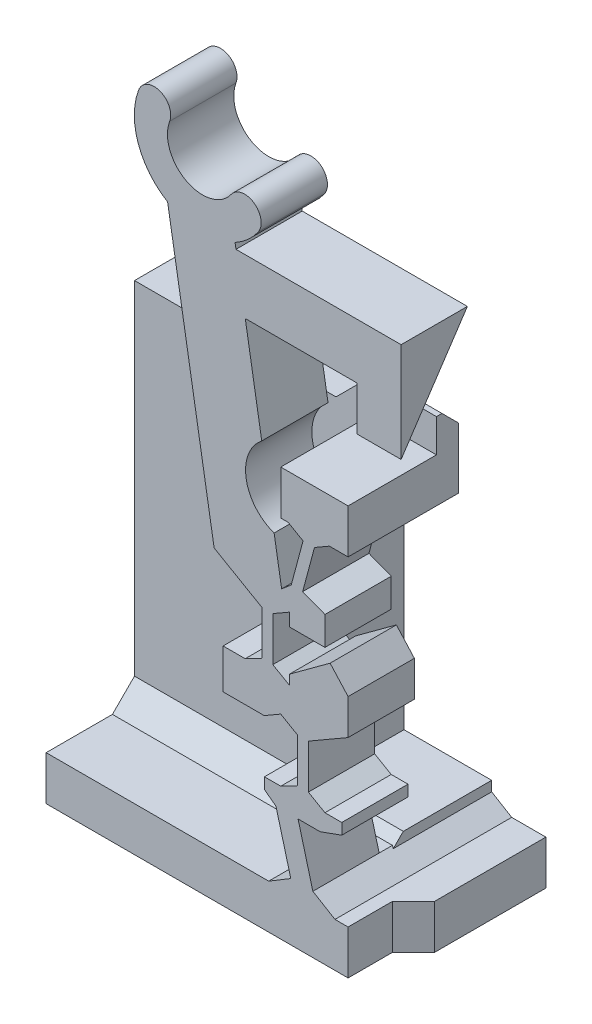
SolidWorks part; units mm, degrees
material "Nylon 6/12"
ref_plane "Front Plane" through (0, 0, 0) normal (0, 0, 1) x (1, 0, 0)
ref_plane "Top Plane" through (0, 0, 0) normal (0, 1, 0) x (1, 0, 0)
ref_plane "Right Plane" through (0, 0, 0) normal (1, 0, 0) x (0, 0, -1)
sketch "Sketch-SkeletonConfigUp" plane through (0, 0, 0) normal (0, 0, 1) x (1, 0, 0)
  line L0 (0, 0) -> (0, -50000) construction
  line L1 (0, 0) -> (4.5811, 6.2164) construction
  line L2 (9.8143, 13.3177) -> (4.5811, 13.945) construction
  line L3 (4.5811, 13.945) -> (2.9713, 10.4094) construction
  line L4 (2.9713, 10.4094) -> (4.5811, 6.2164) construction
  line L5 (4.5811, 13.945) -> (6.2429, 19.1409) construction
  line L6 (2.9713, 10.4094) -> (0.0405, 27.8193) construction
  line L7 (4.5811, 6.2164) -> (9.8143, 13.3177) construction
  line L8 (-587.3593, -797.0242) -> (9.8143, 13.3177) construction
  dimension "D2" = 7.7221
  dimension "D3" = 8.8212
  dimension "D4" = 5.2707
  dimension "D5" = 119.553
  dimension "D6" = 3.8848
  dimension "D7" = 5.4552
  dimension "D8" = 17.6549
  dimension "D9" = 4.4914
  dimension "D10" = 6.745
  dimension "D11" = 145.964
  dimension "D12" = 143.612
sketch "Sketch-SkeletonConfigDown" plane through (0, 0, 0) normal (0, 0, 1) x (1, 0, 0)
  line L0 (0, 0) -> (0, -50000) construction
  line L1 (0, 0) -> (4.5811, 6.2164) construction
  line L2 (9.8143, 13.3177) -> (4.5811, 13.945) construction
  line L3 (4.5811, 13.945) -> (6.1909, 10.4094) construction
  line L4 (6.1909, 10.4094) -> (4.5811, 6.2164) construction
  line L5 (4.5811, 13.945) -> (1.753, 18.6098) construction
  line L6 (6.1909, 10.4094) -> (-8.8652, 19.6294) construction
  line L7 (4.5811, 6.2164) -> (9.8143, 13.3177) construction
  line L8 (-589.9357, -800.5203) -> (9.8143, 13.3177) construction
  dimension "D2" = 7.7221
  dimension "D3" = 8.8212
  dimension "D4" = 5.2707
  dimension "D5" = 119.553
  dimension "D6" = 3.8848
  dimension "D7" = 5.4552
  dimension "D8" = 17.6549
  dimension "D9" = 4.4914
  dimension "D10" = 6.745
  dimension "D11" = 145.964
  dimension "D1" = 143.612
ref_plane "Plane-Cam Base" through (9.128, 0, 0) normal (1, 0, 0) x (0, 0, -1)
ref_plane "Plane-Down-to-Up Derailleur Clearance" through (6.628, 0, 0) normal (1, 0, 0) x (0, 0, -1)
ref_plane "Plane-Cam Cavity Roof" through (5.128, 0, 0) normal (1, 0, 0) x (0, 0, -1)
sketch "Sketch-SwitchBossUp" plane through (0, 0, 0) normal (0, 0, 1) x (1, 0, 0)
  line L0 (3.5811, 11.4759) -> (3.5811, 12.945) construction
  line L5 (5.5811, 12.5552) -> (5.5811, 11.263)
  line L7 (1.5115, 25.1048) -> (1.5536, 24.8548)
  line L8 (-0.4607, 24.7728) -> (1.6885, 12.0057) construction
  line L9 (2.9713, 10.4094) -> (0.0405, 27.8193) construction
  line L11 (0.1364, 21.2256) -> (2.1086, 21.5576) construction
  line L15 (6.628, -23.7286) -> (6.628, 23.7286) construction
  line L16 (2.9713, 10.4094) -> (4.5811, 6.2164) construction
  line L17 (3.5811, 12.945) -> (3.5811, 14.945) construction
  line L18 (5.5811, 12.945) -> (5.5811, 14.945) construction
  line L19 (4.3311, 13.945) -> (4.8311, 13.945) construction
  line L20 (3.5811, 14.945) -> (5.5811, 14.945) construction
  line L21 (3.5811, 12.945) -> (5.5811, 12.945) construction
  line L22 (4.5811, 12.945) -> (4.5811, 14.945) construction
  line L23 (4.5811, 6.2164) -> (8.5405, 7.1023) construction
  line L24 (1.9713, 9.4094) -> (1.9713, 11.4094) construction
  line L25 (3.9713, 9.4094) -> (3.9713, 11.4094) construction
  line L26 (3.9713, 9.4094) -> (1.9713, 9.4094) construction
  line L27 (1.9713, 11.4094) -> (3.9713, 11.4094) construction
  line L28 (3.5811, 7.2164) -> (5.5811, 7.2164) construction
  line L29 (3.5811, 7.2164) -> (3.5811, 5.2164) construction
  line L30 (5.5811, 7.2164) -> (5.5811, 5.2164) construction
  line L31 (3.5811, 5.2164) -> (5.5811, 5.2164) construction
  line L32 (4.8311, 6.2164) -> (4.3311, 6.2164) construction
  line L40 (3.2213, 10.4094) -> (2.7213, 10.4094) construction
  line L66 (0.0405, 27.8193) -> (0.0405, 50027.8193) construction
  line L75 (1.6885, 12.0057) -> (0.5652, 12.6542)
  line L76 (5.5811, 11.263) -> (5.5811, 12.5552) construction
  line L77 (5.5811, 7.6494) -> (6.628, 8.2538)
  line L80 (5.8152, 10.763) -> (6.628, 9.8603)
  line L81 (9.128, 1033.2419) -> (9.128, 20.0586) construction
  line L85 (6.9307, 9.5241) -> (8.5405, 7.7363) construction
  line L88 (5.7256, 17.3347) -> (6.628, 17.3347)
  line L92 (3.7762, 8.3129) -> (6.9307, 9.5241) construction
  line L98 (1.9713, 9.0164) -> (0.9713, 9.0164)
  line L99 (0.9713, 9.0164) -> (0.9713, 7.2164)
  line L100 (0.9713, 7.2164) -> (2.8311, 7.2164)
  line L101 (4.5811, 6.2164) -> (6.9307, 9.5241) construction
  line L103 (0.0405, 27.8193) -> (1.9448, 26.4638) construction
  line L104 (6.9307, 9.5241) -> (8.5405, 7.7363) construction
  line L107 (1.9713, 9.4094) -> (1.9713, 9.0164) construction
  line L109 (0.0405, 27.8193) -> (-2.1498, 28.6358) construction
  line L111 (6.628, 9.8603) -> (6.628, 8.2538)
  line L112 (6.628, 9.8603) -> (6.9307, 9.5241) construction
  line L113 (2.8424, 4.8235) -> (2.8424, 4.3235)
  line L114 (7.3693, 7.7363) -> (7.3563, 7.7363) construction
  line L121 (5.0345, -1.1719) -> (5.0345, 1.4305) construction
  line L122 (9.028, 22.3548) -> (9.028, 20.3548)
  line L127 (5.5811, 15.3347) -> (5.5811, 14.945) construction
  line L130 (6.0345, 0.8281) -> (6.628, 0.8281)
  line L132 (2.8424, 4.3235) -> (3.3646, 3.9305)
  line L133 (2.9713, 10.4094) -> (6.1909, 10.4094) construction
  line L134 (4.5811, 10.4094) -> (4.5811, 13.945) construction
  line L135 (4.5811, 10.4094) -> (4.5811, 6.2164) construction
  line L137 (3.9713, 9.4094) -> (5.5811, 7.2164) construction
  line L139 (5.8152, 10.763) -> (3.9713, 9.4094)
  line L141 (4.0345, 1.4305) -> (3.0345, 0.8281)
  line L142 (3.0345, 0.8281) -> (3.0345, -1.1719)
  line L143 (9.128, 20.0586) -> (9.128, 18.3333) construction
  line L145 (9.128, 16.6071) -> (9.128, -49992.4167) construction
  line L147 (5.5811, 11.263) -> (5.5811, 12.5552) construction
  line L150 (3.0345, -1.1719) -> (5.0345, -1.1719)
  line L151 (3.3646, 3.9305) -> (4.3646, 3.9305) construction
  line L152 (4.5902, 14.945) -> (4.0543, 12.945)
  line L153 (5.1078, 14.945) -> (4.572, 12.945)
  line L157 (3.5811, 17.3347) -> (3.5811, 15.3347)
  line L158 (5.7829, 15.3347) -> (6.628, 15.3347)
  line L162 (3.2213, 11.4094) -> (3.2213, 9.4094)
  line L164 (2.7213, 11.4094) -> (2.7213, 9.4094)
  line L169 (4.3311, 7.2164) -> (4.3311, 5.2164)
  line L170 (4.8311, 5.2164) -> (4.8311, 7.2164)
  line L175 (4.3311, 7.2164) -> (3.5811, 7.6494)
  line L176 (4.8311, 7.2164) -> (5.5811, 7.6494)
  line L177 (5.5811, 7.2164) -> (5.5811, 7.6494) construction
  line L179 (4.3311, 5.2164) -> (3.5811, 4.8235)
  line L180 (3.5811, 5.2164) -> (3.5811, 4.8235) construction
  line L181 (3.5811, 4.8235) -> (2.8424, 4.8235)
  line L183 (4.8311, 5.2164) -> (5.5811, 4.7834)
  line L184 (5.5811, 5.2164) -> (5.5811, 4.7834) construction
  line L186 (9.128, -23.7286) -> (9.128, 23.7286) construction
  line L187 (2.7213, 9.4094) -> (1.9713, 9.0164)
  line L188 (3.2213, 9.4094) -> (3.9713, 8.9764)
  line L189 (3.2213, 11.4094) -> (3.9713, 11.8424)
  line L190 (2.7213, 11.4094) -> (1.6885, 12.0057)
  line L191 (3.9713, 11.4094) -> (3.9713, 11.8424) construction
  line L192 (3.9713, 11.8424) -> (3.9713, 11.263)
  line L193 (4.572, 12.945) -> (5.5811, 12.5552)
  line L194 (4.0543, 12.945) -> (3.6203, 12.5779)
  line L195 (3.9713, 11.263) -> (5.5811, 11.263)
  line L196 (3.9713, 9.4094) -> (3.9713, 8.9764)
  line L197 (3.5811, 7.2164) -> (3.5811, 7.6494) construction
  line L199 (3.5811, 7.6494) -> (2.8311, 7.2164)
  line L201 (2.8424, 4.3235) -> (2.8424, 3.9305) construction
  line L202 (2.8424, 3.9305) -> (3.3646, 3.9305) construction
  line L204 (5.0345, 1.4305) -> (3.0345, 1.4305) construction
  line L205 (3.0345, 1.4305) -> (3.0345, 0.8281) construction
  line L206 (5.0345, 1.4305) -> (6.0345, 0.8281)
  line L207 (9.128, 18.3333) -> (9.128, 16.6071) construction
  line L208 (6.628, -1.1719) -> (6.628, 0.8281)
  line L209 (9.128, 20.0586) -> (9.128, 16.6071) construction
  line L211 (5.0345, 1.4305) -> (4.3646, 3.9305)
  line L212 (4.0345, 1.4305) -> (3.3646, 3.9305)
  line L214 (4.5902, 14.945) -> (3.9152, 15.3347)
  line L215 (3.9152, 15.3347) -> (3.5811, 15.3347)
  line L216 (5.1078, 14.945) -> (5.7829, 15.3347)
  line L217 (5.5811, 12.945) -> (5.5811, 12.5552) construction
  line L218 (5.1078, 14.945) -> (5.1078, 15.3347) construction
  line L219 (5.7829, 15.3347) -> (3.9152, 15.3347) construction
  line L221 (9.028, 22.3548) -> (9.028, 24.8548)
  line L224 (3.5811, 17.3347) -> (5.7256, 17.3347)
  line L232 (6.628, 15.3347) -> (6.628, 17.3347)
  line L233 (6.628, -1.1719) -> (5.0345, -1.1719)
  line L236 (1.5536, 24.8548) -> (9.028, 24.8548)
  line L240 (4.3646, 3.9305) -> (5.3646, 3.9305)
  line L241 (5.3646, 3.9305) -> (6.3424, 4.2834)
  line L248 (7.028, 22.3548) -> (1.9744, 22.3548)
  line L249 (1.9744, 22.3548) -> (2.7198, 17.9273)
  line L250 (9.028, 20.3548) -> (7.028, 20.3548)
  line L251 (7.028, 20.3548) -> (7.028, 22.3548)
  line L252 (3.2801, 14.5986) -> (3.6203, 12.5779)
  line L253 (4.3396, 14.0097) -> (4.8226, 13.8803) construction
  line L254 (0.5652, 12.6542) -> (-1.5413, 25.1678)
  line L367 (5.5811, 4.7834) -> (6.3424, 4.7834)
  line L368 (6.3424, 4.7834) -> (6.3424, 4.2834)
  arc A0 (1.5115, 25.1048) -> (2.5558, 26.0289) centre (0.0405, 27.8193) ccw
  arc A1 (-1.5413, 25.1678) -> (-2.8525, 28.8978) centre (0.0405, 27.8193) cw
  arc A2 (-2.8525, 28.8978) -> (-1.447, 28.3738) centre (-2.1498, 28.6358) cw
  arc A3 (2.5558, 26.0289) -> (1.3338, 26.8987) centre (1.9448, 26.4638) ccw
  arc A4 (-1.447, 28.3738) -> (1.3338, 26.8987) centre (0.0405, 27.8193) ccw
  arc A5 (3.5811, 12.945) -> (3.5811, 14.945) centre (3.2894, 13.945) ccw construction
  arc A6 (5.5811, 12.945) -> (5.5811, 14.945) centre (5.8727, 13.945) cw construction
  arc A7 (2.5699, 9.8686) -> (1.9713, 11.4094) centre (1.6796, 10.4094) ccw construction
  arc A8 (3.9713, 11.4094) -> (3.9713, 9.4094) centre (4.2629, 10.4094) ccw construction
  arc A9 (3.5811, 7.2164) -> (3.5811, 5.2164) centre (3.2895, 6.2164) cw construction
  arc A10 (5.5811, 7.2164) -> (5.5811, 5.2164) centre (5.8728, 6.2164) ccw construction
  circle A28 centre (0.0405, 27.8193) radius 2.3375 construction
  arc A29 (1.9713, 9.4094) -> (2.5699, 9.8686) centre (1.6796, 10.4094) ccw construction
  arc A30 (3.2801, 14.5986) -> (2.7198, 17.9273) centre (3.9114, 16.4164) cw
  arc A31 (-0.4607, 24.7728) -> (-1.5413, 25.1678) centre (0.0405, 27.8193) cw construction
  point P53 (4.5811, 13.945)
  point P63 (2.9713, 10.4094)
  point P93 (1.1225, 21.3916)
  dimension "D23" = 1.5875
  dimension "D24" = 0.75
  dimension "D2" = 2
  dimension "D5" = 2
  dimension "D8" = 42
  dimension "D16" = 42
  dimension "D27" = 120
  dimension "D28" = 120
  dimension "D30" = 120
  dimension "D32" = 120
  dimension "D33" = 120
  dimension "D34" = 120
  dimension "D17" = 0.5
  dimension "D21" = 2
  dimension "D22" = 1
  dimension "D38" = 2
  dimension "D39" = 0.5
  dimension "D40" = 60
  dimension "D41" = 1
  dimension "D42" = 45
  dimension "D43" = 120
  dimension "D10" = 15
  dimension "D12" = 2.5
  dimension "D13" = 1
  dimension "D19" = 1
  dimension "D25" = 15
  dimension "D26" = 120
  dimension "D35" = 120
  dimension "D20" = 3
  dimension "D48" = 2
  dimension "D82" = 1
  dimension "D83" = 3.5
  dimension "D14" = 2.5
  dimension "D15" = 0.25
  dimension "D7" = 2
  dimension "D9" = 2
  dimension "D6" = 0.5
  dimension "D18" = 1.8
  dimension "D29" = 0.5
  dimension "D31" = 1
extrude "Boss-Switch Body" add sketch "Sketch-SwitchBossUp" along normal blind 3
sketch "Sketch1" plane through (0, 0, 0) normal (0, 0, -1) x (-1, 0, 0)
  line L1 (-7.5811, -1.1719) -> (0.4122, -1.1719)
  line L2 (-7.5811, -1.1719) -> (-7.5811, 0.8281)
  line L4 (0.4122, -1.1719) -> (0.4122, 0.8281)
  line L5 (-3.5811, 18.8347) -> (-7.5811, 18.8347)
  line L10 (-7.5811, 18.8347) -> (-7.5811, 15.3347)
  line L11 (-4.0345, 1.4305) -> (-5.0345, 1.4305)
  line L12 (-7.5811, 15.3347) -> (-3.5811, 15.3347)
  line L13 (-4.0345, 1.4305) -> (-3.0345, 0.8281)
  line L14 (-3.5811, 15.3347) -> (-3.5811, 18.8347)
  line L20 (-4.3646, 3.9305) -> (-5.0345, 1.4305) construction
  line L22 (-3.0345, -1.1719) -> (-6.628, -1.1719) construction
  line L23 (-3.0345, 0.8281) -> (0.4122, 0.8281)
  line L24 (-5.0345, 1.4305) -> (-6.0345, 0.8281)
  line L25 (-6.0345, 0.8281) -> (-7.5811, 0.8281)
  dimension "D1" = 3.5
extrude "Boss-Flange Width" add sketch "Sketch1" along normal blind 5
ref_plane "Plane-Sta2Sit Groove" through (0.0405, 0, 0) normal (1, 0, 0) x (0, 0, -1)
ref_plane "Plane-Cam Outer Surface" through (-12.0395, 0, 0) normal (1, 0, 0) x (0, 0, -1)
ref_plane "Plane-FlangeTop" through (-7.0395, 0, 0) normal (1, 0, 0) x (0, 0, -1)
sketch "Sketch2" plane through (-7.0395, 0, 0) normal (1, 0, 0) x (0, 0, -1)
  line L0 (5, 15.3347) -> (-3, 15.3347) construction
  line L1 (5, 17.3347) -> (1, 17.3347)
  line L2 (5, 17.3347) -> (5, 15.3347)
  line L3 (5, 15.3347) -> (1, 15.3347)
  line L4 (1, 17.3347) -> (1, 15.3347)
  line L5 (-3, -1.1719) -> (-3, 0.8281) construction
  line L11 (5, 0.8281) -> (-3, 0.8281)
  line L12 (5, 0.8281) -> (5, -1.1719)
  line L13 (5, -1.1719) -> (-3, -1.1719)
  line L14 (-3, 0.8281) -> (-3, -1.1719)
  line L15 (0, 10.4094) -> (0, 27.8193) construction
  line L17 (5, 0.8281) -> (5, -1.1719) construction
  line L18 (-3, 0.8281) -> (0, 0.8281) construction
  dimension "D1" = 1
  dimension "D2" = 2
extrude "Boss-Flange Height" add sketch "Sketch2" along normal up to surface (11.6675 mm away)
sketch "Sketch10" plane through (0, 15.3347, 0) normal (0, 1, 0) x (1, 0, 0)
  line L0 (9.128, -23.7286) -> (9.128, 23.7286) construction
  line L1 (7.5811, 5) -> (5.128, 5)
  line L2 (7.5811, 5) -> (7.5811, 2)
  line L3 (7.5811, 2) -> (5.128, 2)
  line L5 (4.628, 7) -> (4.628, 1) construction
  line L6 (3.5811, 1) -> (-7.0395, 1) construction
  line L8 (5.128, 5) -> (5.128, 2)
  dimension "D1" = 1
  dimension "D2" = 0.5
  dimension "D3" = 4.5
extrude "Cut-Up-To-Down Derailleur Clearance" cut sketch "Sketch10" along normal up to next
sketch "Sketch17" plane through (0, 15.3347, 0) normal (0, -1, 0) x (1, 0, 0)
  line L0 (5.128, -5) -> (-7.0395, -5)
  line L1 (5.128, -5) -> (-7.0395, -5) construction
  line L2 (-7.0395, -5) -> (-7.0395, -1)
  line L3 (-7.0395, -1) -> (5.128, -1)
  line L4 (5.128, -1) -> (5.128, -5)
  line L5 (-7.0395, -1) -> (-7.0395, -5) construction
extrude "Boss-Flange Support" add sketch "Sketch17" along normal up to surface (14.5065 mm away) up to face at (-2.0025, 0.8281, -1)
sketch "Sketch-HolePositions" plane through (0, -1.1719, 0) normal (0, -1, 0) x (1, 0, 0)
  line L0 (-7.0395, -3) -> (7.5811, -3) construction
  line L1 (7.5811, -5) -> (-7.0395, -5) construction
  line L2 (7.5811, -5) -> (7.5811, 0) construction
  line L4 (-7.0395, -22.2167) -> (-7.0395, 22.2167) construction
  point P6 (-5.0395, -3)
  point P7 (-0.5395, -3)
  dimension "D1" = 2
  dimension "D2" = 4.5
  dimension "D3" = 2
sketch "Sketch6" plane through (0, -1.1719, 0) normal (0, -1, 0) x (-1, 0, 0)
  point P0 (5.0395, 3)
  point P3 (0.5395, 3)
hole_wizard "Tap Drill for M2x0.4 Tap1" positions "Sketch6" profile "Sketch5" hole size "M2x0.4" standard "ANSI Metric" end condition through all
sketch "Sketch5" plane through (-5.0395, -1.1719, -3) normal (1, 0, 0) x (0, 0, -1)
  line L0 (0, 0) -> (0, 30.5577)
  line L1 (0, 30.5577) -> (0.8, 30.5577)
  line L2 (0.8, 30.5577) -> (0.8, 0)
  line L5 (0.8, 0) -> (0, 0)
  line L11 (0, -6.35) -> (0, 107.95) construction
  dimension "Thru Hole Dia." = 1.6
  dimension "Thru Hole Depth" = 30.5577
sketch "Sketch9" plane through (0, -1.1719, 0) normal (0, -1, 0) x (1, 0, 0)
  point P0 (-5.0395, -3)
  point P3 (-0.5395, -3)
hole_wizard "M2 Clearance Hole2" positions "Sketch9" profile "Sketch8" hole size "M2" standard "ANSI Metric"
sketch "Sketch8" plane through (-5.0395, -1.1719, -3) normal (1, 0, 0) x (0, 0, -1)
  line L0 (0, 0) -> (0, 15.721)
  line L1 (0, 15.721) -> (1.2, 15)
  line L2 (1.2, 15) -> (1.2, 0)
  line L5 (1.2, 0) -> (0, 0)
  line L10 (0, 15.721) -> (-1.2, 15) construction
  line L11 (0, -6.35) -> (0, 107.95) construction
  dimension "Hole Dia." = 2.4
  dimension "Hole Depth" = 15
  dimension "Drill Angle" = 118
sketch "Sketch-Measurements for Derailleur Ramps" [suppressed] plane through (0, 0, 0) normal (0, 0, 1) x (1, 0, 0)
  line L0 (3.184, 15.1695) -> (2.4687, 19.4188)
  line L1 (2.8264, 17.2941) -> (1.8402, 17.1281)
  line L2 (2.9713, 10.4094) -> (0.0405, 27.8193) construction
  line L3 (1.8402, 17.1281) -> (-1.3081, 15.0016)
  line L4 (6.1909, 10.4094) -> (-8.8652, 19.6294) construction
  line L5 (1.8402, 17.1281) -> (2.6012, 12.6077)
  line L6 (2.6012, 12.6077) -> (-1.3081, 15.0016)
  line L7 (0.2661, 16.0649) -> (0.2661, 17.1281)
  line L8 (0.2661, 17.1281) -> (1.8402, 17.1281)
  line L9 (6.1909, 10.4094) -> (2.9713, 10.4094)
  line L10 (5.386, 8.3129) -> (3.7762, 8.3129)
  line L11 (2.6116, 18.5698) -> (1.5115, 25.1048) construction
  line L12 (6.1909, 10.4094) -> (4.5811, 6.2164) construction
  line L13 (4.5811, 8.3129) -> (4.5811, 8.7912)
  line L14 (4.5811, 6.2164) -> (5.386, 8.3129)
  line L15 (2.9713, 10.4094) -> (4.5811, 6.2164) construction
  line L16 (3.7762, 8.3129) -> (4.5811, 6.2164)
  line L17 (5.386, 8.3129) -> (5.386, 8.7912)
  dimension "D1" = 1.5742
  dimension "D2" = 0.8049
ref_plane "Plane1" through (0, 7.1023, 0) normal (0, 1, 0) x (1, 0, 0)
ref_plane "Plane-Cantilever Cut" [suppressed] through (7.0848, 8.5204, -1.9058) normal (-0.6301, -0.7578, 0.1695) x (-0.7765, 0.6151, -0.1368)
sketch "Sketch14" [suppressed] plane through (7.0848, 8.5204, -1.9058) normal (-0.6301, -0.7578, 0.1695) x (-0.7765, 0.6151, -0.1368)
  line L0 (2.3023, -1.6911) -> (-0.3551, -1.6911)
  line L2 (2.3023, -4.3362) -> (2.3023, -1.6911)
  line L3 (-0.3551, -1.6911) -> (-0.3551, -4.4608)
  line L5 (-0.3551, -4.4608) -> (1.0087, -5.0843)
  line L6 (1.0087, -5.0843) -> (2.3023, -4.3362)
extrude "Cut-Down-to-Up Cantilever Slope" [suppressed] cut sketch "Sketch14" against normal up to next
ref_plane "Plane-Symmetry Plane" through (0, 0, 1.5) normal (0, 0, 1) x (1, 0, 0)
sketch "Sketch-Cable Center Point" plane through (0, 0, 1.5) normal (0, 0, 1) x (1, 0, 0)
  line L0 (0.0405, 27.8193) -> (0.1722, 27.0366)
  line L1 (2.9713, 10.4094) -> (0.0405, 27.8193) construction
  point P0 (0.0405, 27.8193)
  dimension "D1" = 0.7937
chamfer "Chamfer-Flange Support" distance 1.5 angle 45 1 edges at (3.5811, 17.3347, -3)
chamfer "Chamfer-Flange Support 2" distance 1.5 angle 45 2 edges at (5.128, 17.0847, -2) (5.128, 15.3347, -1.5)
chamfer "Chamfer-Flange Support 3" distance 1 angle 45 1 edges at (-2.0025, 0.8281, -1)
chamfer "Chamfer7" [suppressed] distance 1 angle 45
sketch "Sketch23" plane through (0, 0, -1) normal (0, 0, 1) x (1, 0, 0)
  line L0 (5.128, 1.8281) -> (1.1605, 1.8281)
  line L1 (-7.0395, 1.8281) -> (5.128, 1.8281) construction
  line L2 (1.1605, 1.8281) -> (1.1605, 13.8347)
  line L3 (1.1605, 13.8347) -> (5.128, 13.8347)
  line L4 (5.128, 13.8347) -> (5.128, 1.8281)
  line L5 (0.6605, -1.1719) -> (0.6605, 13.8281) construction
  dimension "D1" = 0.5
extrude "Cut-Gap for Printing" cut sketch "Sketch23" against normal through all
sketch "Sketch25" plane through (0, 0, 0) normal (0, 0, 1) x (1, 0, 0)
  line L0 (6.628, 15.3347) -> (7.5811, 15.3347)
  line L1 (7.5811, 15.3347) -> (7.5811, 18.8347)
  line L2 (7.5811, 18.8347) -> (6.628, 18.8347)
  line L3 (6.628, -23.7286) -> (6.628, 23.7286) construction
  line L4 (7.5811, 18.8347) -> (3.5811, 18.8347) construction
  line L5 (6.628, 18.8347) -> (6.628, 15.3347)
  line L6 (7.5811, 18.8347) -> (7.5811, 15.3347) construction
extrude "Cut-Derailleur Clearance" cut sketch "Sketch25" against normal through all
chamfer "Chamfer8" distance 1 angle 45 1 edges at (6.628, -0.1719, 0)
ref_plane "Plane2" through (-3.0866, 5.589, 8.3835) normal (0.2929, -0.5304, -0.7956) x (-0.9561, -0.1625, -0.2437)
sketch "Sketch26" plane through (-3.0866, 5.589, 8.3835) normal (0.2929, -0.5304, -0.7956) x (-0.9561, -0.1625, -0.2437)
  line L0 (-7.553, 20.6804) -> (-7.553, 14.9094)
  line L1 (-12.6703, 20.6804) -> (-5.5238, 20.6804) construction
  line L3 (-7.553, 14.9094) -> (-20.0302, 14.9094)
  line L4 (-20.0302, 14.9094) -> (-20.0302, 20.6804)
  line L5 (-20.0302, 20.6804) -> (-7.553, 20.6804)
extrude "Cut-Up-to-Down Cantilever Slope" cut sketch "Sketch26" along normal up to next
sketch "Sketch27" plane through (5.128, 0, 0) normal (1, 0, 0) x (0, 0, -1)
  line L0 (3.5, 18.8347) -> (3.5, 13.8347) construction
  line L1 (2.5, 18.8347) -> (5, 18.8347)
  line L2 (2.5, 18.8347) -> (2.5, 13.8347)
  line L3 (2.5, 13.8347) -> (5, 13.8347)
  line L4 (5, 18.8347) -> (5, 13.8347)
  dimension "D1" = 1
extrude "Cut-Wide Derailleur Clearance" cut sketch "Sketch27" against normal blind 4 and the other way through all
chamfer "Chamfer9" distance 1.25 angle 45 1 edges at (4.8545, 18.8347, -2.5)
sketch "Sketch28" plane through (0, 0, -1) normal (0, 0, 1) x (1, 0, 0)
  line L0 (3.5811, 18.8347) -> (6.628, 18.8347)
  line L1 (6.628, 18.8347) -> (6.628, 17.3347)
  line L2 (6.628, 17.3347) -> (3.5811, 17.3347)
  line L3 (3.5811, 17.3347) -> (3.5811, 18.8347)
extrude "Cut-Extrude1" cut sketch "Sketch28" along normal up to surface (1 mm away) up to face at (5.1045, 18.0847, 0)
equation "\"axle-diameter\"=2"
equation "\"switch-thickness\"=12"
equation "\"base-width\"=4.0"
equation "\"axle-bushing-radius\"=3"
equation "\"clearance\"= 0.25"
equation "\"arm-width\"=1.5"
equation "\"min-diameter\"=70"
equation "\"alpha\"=143.6120"
equation "\"gamma\"=119.5526"
equation "\"delta\"=145.9637"
equation "\"epsilon\"=6.7452"
equation "\"l_AB\"=8.8212"
equation "\"l_AC\"=4.4914"
equation "\"l_BD\"=5.2707"
equation "\"l_CD\"=3.8848"
equation "\"l_CE\"=17.6549"
equation "\"l_DF\"=5.4552"
equation "\"l_OA\"=7.7221"
equation "\"D2@Sketch-SkeletonConfigUp\" = \"l_OA\""
equation "\"D3@Sketch-SkeletonConfigUp\" = \"l_AB\""
equation "\"D4@Sketch-SkeletonConfigUp\" = \"l_BD\""
equation "\"D5@Sketch-SkeletonConfigUp\" = \"gamma\""
equation "\"D6@Sketch-SkeletonConfigUp\" = \"l_CD\""
equation "\"D7@Sketch-SkeletonConfigUp\" = \"l_DF\""
equation "\"D8@Sketch-SkeletonConfigUp\" = \"l_CE\""
equation "\"D9@Sketch-SkeletonConfigUp\" = \"l_AC\""
equation "\"D_groove\"=3.175"
equation "\"D7@Sketch-SkeletonConfigDown\" = \"l_DF\""
equation "\"D6@Sketch-SkeletonConfigDown\" = \"l_CD\""
equation "\"D2@Sketch-SkeletonConfigDown\" = \"l_OA\""
equation "\"D3@Sketch-SkeletonConfigDown\" = \"l_AB\""
equation "\"D9@Sketch-SkeletonConfigDown\" = \"l_AC\""
equation "\"D8@Sketch-SkeletonConfigDown\" = \"l_CE\""
equation "\"D5@Sketch-SkeletonConfigDown\" = \"gamma\""
equation "\"D4@Sketch-SkeletonConfigDown\" = \"l_BD\""
equation "\"D1@Sketch-SkeletonConfigDown\" = \"alpha\""
equation "\"hinge_length\"=1.5"
equation "\"hinge_depth\"=0.25"
equation "\"D10@Sketch-SkeletonConfigUp\"=\"epsilon\""
equation "\"D11@Sketch-SkeletonConfigUp\"=\"delta\""
equation "\"D12@Sketch-SkeletonConfigUp\"=\"alpha\""
equation "\"D11@Sketch-SkeletonConfigDown\"=\"delta\""
equation "\"D10@Sketch-SkeletonConfigDown\"=\"epsilon\""
equation "\"EE_dx\"=8.9056"
equation "\"EE_dy\"=8.1898"
equation "\"r_groove\"=\"D_groove\"/2"
equation "\"t_wall\"=25.4/16"
equation "\"width_lower\"=\"D_groove\"+\"t_wall\""
equation "\"cable_to_bottom\"=30.6257"
equation "\"switch_EE-up_base_dy\"=24"
equation "\"switch_EE-down_base_dy\"=16"
equation "\"D_axle\"=25.4/8"
equation "\"D_up_to_down\"=16"
equation "\"D_down_to_up\"=25"
equation "\"t_cam_base\"=7.5"
equation "\"D23@Sketch-SwitchBossUp\"=\"D_groove\"/2"
equation "\"D1@Sketch-Cable Center Point\"=\"D_groove\"/4"
